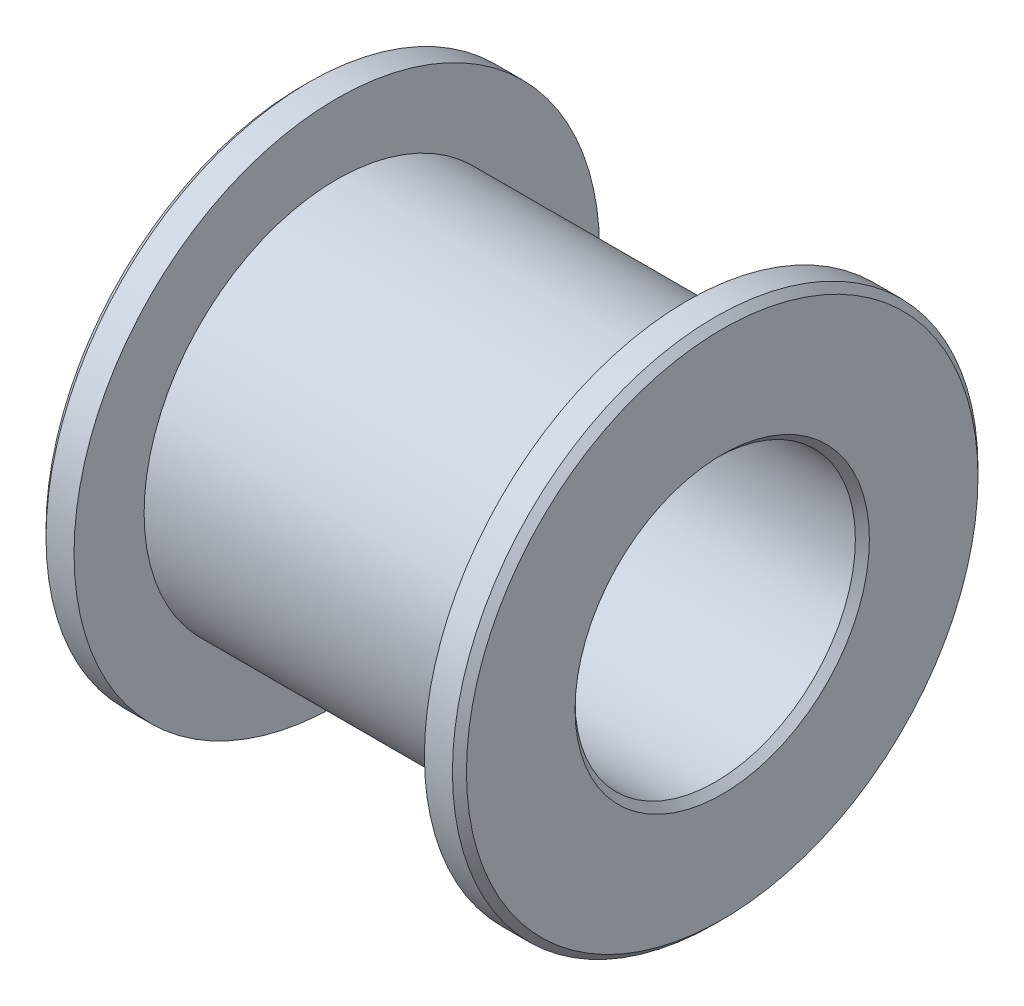
SolidWorks part; units mm, degrees
ref_plane "Front Plane" through (0, 0, 0) normal (0, 0, 1) x (1, 0, 0)
ref_plane "Top Plane" through (0, 0, 0) normal (0, 1, 0) x (1, 0, 0)
ref_plane "Right Plane" through (0, 0, 0) normal (1, 0, 0) x (0, 0, -1)
sketch "Sketch1" plane through (0, 0, 0) normal (0, 0, 1) x (1, 0, 0)
  line L0 (0, 5.5) -> (-5, 5.5)
  line L1 (-5, 5.5) -> (-5, 7.5)
  line L2 (-5, 7.5) -> (-6, 7.5)
  line L3 (-6, 7.5) -> (-6, 0)
  line L4 (-6, 0) -> (0, 0)
  line L5 (0, 0) -> (0, 5.5)
  dimension "D1" = 5.5
  dimension "D2" = 7.5
  dimension "D3" = 1
  dimension "D4" = 5
revolve "Revolve1" add sketch "Sketch1" angle 360 about L4
mirror "Mirror1" about plane through (0, 0, 0) normal (1, 0, 0) of "Revolve1"
sketch "Sketch2" plane through (-6, 0, 0) normal (-1, 0, 0) x (0, 0, 1)
  circle A0 centre (0, 0) radius 4
  dimension "D1" = 8
extrude "Cut-Extrude1" cut sketch "Sketch2" against normal through all both and the other way through all
chamfer "Chamfer1" distance 0.2 angle 45 4 edges at (6, 0, 4) (-6, 0, -4) (6, 0, 7.5) (-6, 0, 7.5)
ref_plane "Plane2" through (0, -3.4641, 2) normal (0, 0.866, -0.5) x (-1, 0, 0)
sketch "Sketch4" plane through (0, -3.4641, 2) normal (0, 0.866, -0.5) x (-1, 0, 0)
  circle A0 centre (0, 0) radius 1.5
  dimension "D1" = 3
extrude "Cut-Extrude2" cut sketch "Sketch4" along normal blind 5 and the other way blind 5
